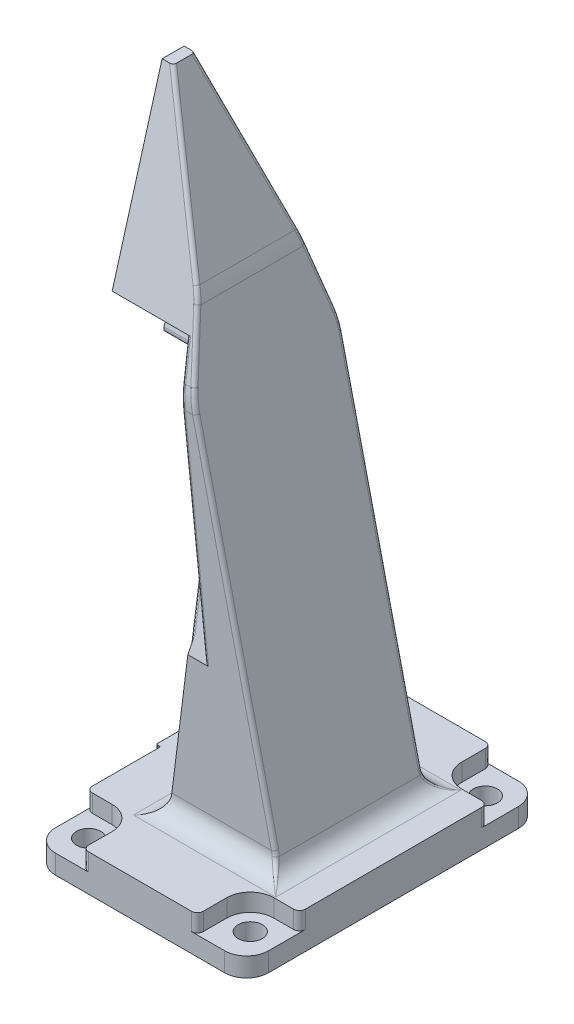
SolidWorks part; units mm, degrees
ref_plane "前视基准面" through (0, 0, 0) normal (0, 0, 1) x (1, 0, 0)
ref_plane "上视基准面" through (0, 0, 0) normal (0, 1, 0) x (1, 0, 0)
ref_plane "右视基准面" through (0, 0, 0) normal (1, 0, 0) x (0, 0, -1)
other "Configuration Table"
sketch "草图1" plane through (0, 0, 0) normal (0, 1, 0) x (1, 0, 0)
  line L1 (-14.5, -20) -> (14.5, -20)
  line L2 (-14.5, -20) -> (-14.5, 20)
  line L3 (-14.5, 20) -> (14.5, 20)
  line L4 (14.5, -20) -> (14.5, 20)
  line L5 (-14.5, -20) -> (14.5, 20) construction
  line L6 (-14.5, 20) -> (14.5, -20) construction
  line L7 (-11, -16) -> (11, -16) construction
  line L8 (-11, -16) -> (-11, 16) construction
  line L9 (-11, 16) -> (11, 16) construction
  line L10 (11, -16) -> (11, 16) construction
  line L11 (-11, -16) -> (11, 16) construction
  line L12 (-11, 16) -> (11, -16) construction
  circle A0 centre (-11, 16) radius 1.65
  circle A1 centre (11, 16) radius 1.65
  circle A2 centre (11, -16) radius 1.65
  circle A3 centre (-11, -16) radius 1.65
  point P0 (0, 0)
  point P5 (0, 0)
extrude "凸台-拉伸1" add sketch "草图1" along normal blind 5
fillet "圆角1" radius 3 4 edges at (14.5, 2.5, -20) (-14.5, 2.5, -20) (-14.5, 2.5, 20) (14.5, 2.5, 20)
sketch "草图2" plane through (0, 0, 0) normal (0, 0, 1) x (1, 0, 0)
  line L0 (-15.5, 85) -> (-14, 85)
  line L1 (9, 5) -> (-15.5, 5)
  line L2 (-15.5, 85) -> (-15.5, 5)
  line L3 (-14, 85) -> (-5, 65)
  line L4 (-5, 65) -> (9, 5)
extrude "凸台-拉伸2" add sketch "草图2" along normal mid plane 20
sketch "草图3" plane through (-15.5, 0, 0) normal (-1, 0, 0) x (0, 0, 1)
  line L0 (-1.5, 85) -> (-10, 55)
  line L1 (10, 85) -> (-10, 85) construction
  line L2 (-10, 85) -> (-10, 5) construction
  line L3 (-10, 55) -> (-10, 85)
  line L4 (-10, 85) -> (-1.5, 85)
  line L5 (1.5, 85) -> (10, 85)
  line L6 (10, 85) -> (10, 55)
  line L7 (10, 85) -> (10, 5) construction
  line L8 (10, 55) -> (1.5, 85)
extrude "切除-拉伸1" cut sketch "草图3" against normal up to surface (30 mm away) up to face at (14.5, 2.5, 0)
sketch "草图4" plane through (-15.5, 0, 0) normal (-1, 0, 0) x (0, 0, 1)
  line L12 (-8.3, 61) -> (-10, 55)
  line L15 (-8.3, 61) -> (-1.0875, 53.7875)
  line L16 (-10, 55) -> (-1.5, 85) construction
  line L18 (-8.3, 53.7875) -> (-1.0875, 53.7875)
  line L19 (8.3, 61) -> (1.0875, 53.7875)
  line L20 (1.5, 85) -> (10, 55) construction
  line L23 (1.0875, 53.7875) -> (8.3, 53.7875)
  line L25 (-10, 55) -> (-10, 53.7875)
  line L26 (-10, 55) -> (-10, 5) construction
  line L27 (-10, 53.7875) -> (-8.3, 53.7875)
  line L28 (8.3, 61) -> (10, 55)
  line L29 (10, 55) -> (10, 53.7875)
  line L30 (10, 55) -> (10, 5) construction
  line L31 (10, 53.7875) -> (8.3, 53.7875)
extrude "切除-拉伸2" cut sketch "草图4" against normal blind 10.2
sketch "草图6" plane through (-15.5, 0, 0) normal (-1, 0, 0) x (0, 0, 1)
  line L1 (10, 53.7875) -> (10, 5) construction
  line L4 (-10, 53.7875) -> (-10, 5) construction
  line L5 (-10, 25) -> (-1.0875, 53.7875) construction
  line L6 (1.0875, 53.7875) -> (10, 25) construction
ref_plane "基准面2" through (0, 5.0118, 16.1883) normal (0, 0.2957, 0.9553) x (1, 0, 0)
sketch "草图8" plane through (0, 5.0118, 16.1883) normal (0, 0.2957, 0.9553) x (1, 0, 0)
  line L10 (-15.5, 51.0598) -> (-5.3, 51.0598)
  line L11 (-5.3, 51.0598) -> (-1, 20)
  line L12 (-1, 20) -> (-15.5, 20)
  line L13 (-15.5, 51.0598) -> (-15.5, 20.9242) construction
  line L14 (-15.5, 48.4239) -> (-15.5, 1.8189) construction
  line L15 (-15.5, 20) -> (-15.5, 51.0598)
extrude "切除-拉伸3" cut sketch "草图8" along normal through all
ref_plane "基准面3" through (0.5193, 0.0575, -0.0575) normal (-0.988, -0.1093, 0.1093) x (0.1087, 0.012, 0.994)
sketch "草图10" plane through (0.5193, 0.0575, -0.0575) normal (-0.988, -0.1093, 0.1093) x (0.1087, 0.012, 0.994)
  line L3 (10.1181, 62.9025) -> (1.1519, 54.0441)
  line L4 (1.1519, 54.0441) -> (10.1181, 24.9724)
  line L5 (10.1181, 24.9724) -> (10.1181, 62.9025)
extrude "切除-拉伸4" cut sketch "草图10" along normal through all
ref_plane "基准面4" through (0, 5.0118, -16.1883) normal (0, 0.2957, -0.9553) x (-1, 0, 0)
sketch "草图11" plane through (0, 5.0118, -16.1883) normal (0, 0.2957, -0.9553) x (-1, 0, 0)
  line L5 (15.5, 51.0598) -> (5.3, 51.0598)
  line L6 (5.3, 51.0598) -> (1, 20)
  line L7 (1, 20) -> (15.5, 20)
  line L8 (15.5, 48.4239) -> (15.5, 1.8189) construction
  line L9 (15.5, 20) -> (15.5, 51.0598)
extrude "切除-拉伸5" cut sketch "草图11" along normal through all
ref_plane "基准面5" through (0.5193, 0.0575, 0.0575) normal (-0.988, -0.1093, -0.1093) x (-0.1087, -0.012, 0.994)
sketch "草图14" plane through (0.5193, 0.0575, 0.0575) normal (-0.988, -0.1093, -0.1093) x (-0.1087, -0.012, 0.994)
  line L3 (-10.1181, 62.9025) -> (-1.1519, 54.0441)
  line L4 (-1.1519, 54.0441) -> (-10.1181, 24.9724)
  line L5 (-10.1181, 24.9724) -> (-10.1181, 62.9025)
extrude "切除-拉伸6" cut sketch "草图14" along normal through all
sketch "草图15" plane through (0, 0, -10) normal (0, 0, -1) x (-1, 0, 0)
  line L8 (15.5, 52.5) -> (7.5, 52.5)
  line L9 (15.5, 25) -> (15.5, 53.7875) construction
  line L10 (7.5, 52.5) -> (3.5, 25)
  line L11 (15.5, 25) -> (1.1279, 25) construction
  line L14 (6, 5) -> (15.5, 5)
  line L15 (15.5, 5) -> (15.5, 52.5)
  line L16 (3.5, 25) -> (6, 5)
extrude "切除-拉伸7" cut sketch "草图15" against normal up to surface (20 mm away) up to face at (-6.3918, 25, 10)
fillet "圆角2" radius 3 1 edges at (-7.5, 52.5, 0)
fillet "圆角3" radius 0.6 6 edges at (-5.3132, 37.4659, 6.1406) (-8.1325, 51.7689, 1.7125) (-5.3132, 37.4659, -6.1406) (-8.1325, 51.7689, -1.7125) (-12.7976, 52.5, 1.4861) (-12.7976, 52.5, -1.4861)
fillet "圆角4" radius 10 3 edges at (-5, 65, 0) (-3.5573, 55, 10) (-3.5573, 55, -10)
fillet "圆角5" radius 2.6 4 edges at (1.5, 5, 10) (9, 5, 0) (1.5, 5, -10) (-6, 5, 0)
fillet "圆角6" radius 0.5 14 edges at (9.447, 5.5633, -10.9838) (8.4627, 7.3027, -10.0171) (3.0254, 30.6053, -10) (-2.6636, 54.9868, -9.9049) (-9.6993, 75.4428, -4.2079) (-5.0446, 64.9849, -7.1709) (9.447, 5.5633, 10.9838) (8.4627, 7.3027, 10.0171) (3.0254, 30.6053, 10) (-2.6636, 54.9868, 9.9049) (-3.8789, 60.1955, 8.5279) (-5.0446, 64.9849, 7.1709) (-3.8789, 60.1955, -8.5279) (-9.6993, 75.4428, 4.2079)
fillet "圆角7" radius 0.5 6 edges at (-4.9689, 58.6684, -8.9606) (-4.4569, 54.9868, -9.9049) (-4.9689, 58.6684, 8.9606) (-4.4569, 54.9868, 9.9049) (-2.711, 39.3053, -10) (-2.711, 39.3053, 10)
sketch "草图16" plane through (0, 0, 0) normal (0, -1, 0) x (1, 0, 0)
  line L0 (-14.7, 2.7) -> (-14.9, 2.7)
  line L2 (-15.1, 2.5) -> (-15.1, -2.5)
  line L3 (-14.9, -2.7) -> (-14.7, -2.7)
  line L5 (-14.5, -17) -> (-14.5, 17) construction
  line L7 (-14.5, -2.9) -> (-14.5, 2.9)
  arc A1 (-14.9, -2.7) -> (-15.1, -2.5) centre (-14.9, -2.5) cw
  arc A3 (-15.1, 2.5) -> (-14.9, 2.7) centre (-14.9, 2.5) cw
  arc A4 (-14.5, -2.9) -> (-14.7, -2.7) centre (-14.7, -2.9) ccw
  arc A5 (-14.5, 2.9) -> (-14.7, 2.7) centre (-14.7, 2.9) cw
  point P0 (-15.1, 0)
  dimension "D1" = 0.2
  dimension "D3" = 0.2
  dimension "D4" = 14.5
  dimension "D5" = 0.2
  dimension "D6" = 0.2
  dimension "D2" = 5
  dimension "D7" = 0.6
extrude "凸台-拉伸3" add sketch "草图16" against normal up to surface (5 mm away) up to face at (1.384, 5, 0)
sketch "草图17" plane through (0, 5, 0) normal (0, 1, 0) x (1, 0, 0)
  line L0 (-7.8, 16) -> (-7.8, 20)
  line L1 (11.5, 20) -> (-11.5, 20) construction
  line L2 (-11, 12.8) -> (-14.5, 12.8)
  line L3 (-14.5, 17) -> (-14.5, 2.9) construction
  line L4 (7.8, 16) -> (7.8, 20)
  line L5 (11, 12.8) -> (14.5, 12.8)
  line L6 (-7.8, -16) -> (-7.8, -20)
  line L7 (-11, -12.8) -> (-14.5, -12.8)
  line L8 (7.8, -16) -> (7.8, -20)
  line L9 (11, -12.8) -> (14.5, -12.8)
  line L10 (-7.8, 20) -> (-11.5, 20)
  line L11 (14.5, 12.8) -> (14.5, 17)
  line L12 (-14.5, 17) -> (-14.5, 2.9)
  line L13 (-14.7, 2.7) -> (-14.9, 2.7)
  line L14 (-15.1, 2.5) -> (-15.1, -2.5)
  line L15 (-14.9, -2.7) -> (-14.7, -2.7)
  line L16 (-14.5, -2.9) -> (-14.5, -17)
  line L17 (-11.5, -20) -> (11.5, -20)
  line L18 (14.5, -17) -> (14.5, 17)
  line L19 (11.5, 20) -> (-11.5, 20)
  line L20 (-14.5, 17) -> (-14.5, 12.8)
  line L24 (-14.5, -12.8) -> (-14.5, -17)
  line L25 (-11.5, -20) -> (-7.8, -20)
  line L26 (14.5, -17) -> (14.5, -12.8)
  line L27 (11.5, 20) -> (7.8, 20)
  line L28 (7.8, -20) -> (11.5, -20)
  arc A0 (-11, 12.8) -> (-7.8, 16) centre (-11, 16) ccw
  arc A1 (7.8, 16) -> (11, 12.8) centre (11, 16) ccw
  arc A2 (11, -12.8) -> (7.8, -16) centre (11, -16) ccw
  arc A3 (-7.8, -16) -> (-11, -12.8) centre (-11, -16) ccw
  arc A13 (-14.9, 2.7) -> (-15.1, 2.5) centre (-14.9, 2.5) ccw
  arc A14 (-15.1, -2.5) -> (-14.9, -2.7) centre (-14.9, -2.5) ccw
  arc A16 (-14.5, -17) -> (-11.5, -20) centre (-11.5, -17) ccw
  arc A17 (11.5, -20) -> (14.5, -17) centre (11.5, -17) ccw
  arc A18 (14.5, 17) -> (11.5, 20) centre (11.5, 17) ccw
  arc A19 (-11.5, 20) -> (-14.5, 17) centre (-11.5, 17) ccw
  arc A24 (-14.5, -17) -> (-11.5, -20) centre (-11.5, -17) ccw
  arc A25 (11.5, -20) -> (14.5, -17) centre (11.5, -17) ccw
  arc A26 (14.5, 17) -> (11.5, 20) centre (11.5, 17) ccw
  arc A27 (-11.5, 20) -> (-14.5, 17) centre (-11.5, 17) ccw
  arc A28 (-14.7, 2.7) -> (-14.5, 2.9) centre (-14.7, 2.9) ccw
  arc A30 (-14.5, -2.9) -> (-14.7, -2.7) centre (-14.7, -2.9) ccw
  dimension "D1" = 0
extrude "切除-拉伸8" cut sketch "草图17" against normal blind 2.4
fillet "圆角8" radius 0.8 8 edges at (-14.5, 3.8, 12.8) (-7.8, 3.8, 20) (7.8, 3.8, 20) (14.5, 3.8, 12.8) (14.5, 3.8, -12.8) (7.8, 3.8, -20) (-14.5, 3.8, -12.8) (-7.8, 3.8, -20)
